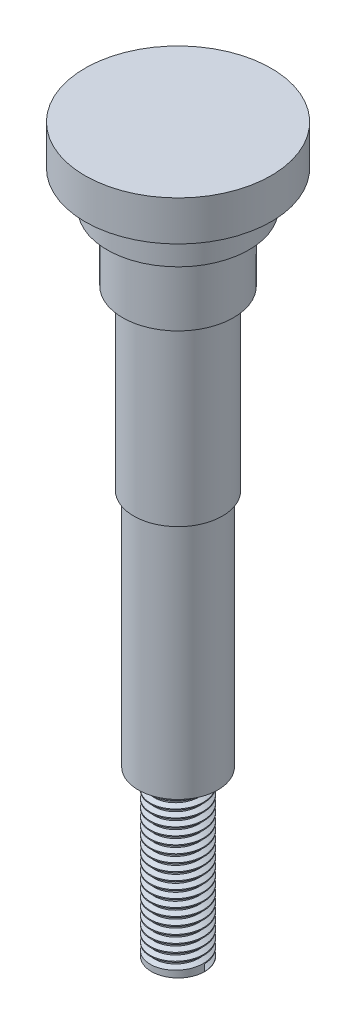
SolidWorks part; units mm, degrees
ref_plane "Front Plane" through (0, 0, 0) normal (0, 0, 1) x (1, 0, 0)
ref_plane "Top Plane" through (0, 0, 0) normal (0, 1, 0) x (1, 0, 0)
ref_plane "Right Plane" through (0, 0, 0) normal (1, 0, 0) x (0, 0, -1)
sketch "Sketch2" plane through (0, 0, 0) normal (0, 1, 0) x (1, 0, 0)
  circle A0 centre (0, 0) radius 21
extrude "Boss-Extrude1" add sketch "Sketch2" along normal blind 9
sketch "Sketch3" plane through (0, 0, 0) normal (0, -1, 0) x (1, 0, 0)
  circle A0 centre (0, 0) radius 16
extrude "Boss-Extrude2" add sketch "Sketch3" along normal blind 8
sketch "Sketch4" plane through (0, -8, 0) normal (0, -1, 0) x (1, 0, 0)
  circle A0 centre (0, 0) radius 12.5
extrude "Boss-Extrude3" add sketch "Sketch4" along normal blind 15
sketch "Sketch5" plane through (0, -23, 0) normal (0, -1, 0) x (1, 0, 0)
  circle A0 centre (0, 0) radius 10
extrude "Boss-Extrude4" add sketch "Sketch5" along normal blind 40
sketch "Sketch6" plane through (0, -63, 0) normal (0, -1, 0) x (1, 0, 0)
  circle A0 centre (0, 0) radius 9
extrude "Boss-Extrude5" add sketch "Sketch6" along normal blind 54
sketch "Sketch7" plane through (0, -117, 0) normal (0, -1, 0) x (1, 0, 0)
  circle A0 centre (0, 0) radius 6
extrude "Boss-Extrude6" add sketch "Sketch7" along normal blind 37
thread "Thread1" pitch 1.75 method cut profile "Thread Profile1" start angle 0, offset 0, length 0, pitch 1.75, diameter 12
ref_plane "Plane1" through (6, -154, 0) normal (0, 0, 1) x (1, 0, 0)
sketch "Thread Profile1" plane through (6, -154, 0) normal (0, 0, 1) x (1, 0, 0)
  line L0 (0, 0) -> (0, 1.75) construction
  line L11 (0, 0) -> (0, 1.5312)
  line L12 (0, 1.5312) -> (-0.9472, 0.9844)
  line L13 (-0.9472, 0.9844) -> (-0.9472, 0.5469)
  line L15 (-0.9472, 0.5469) -> (0, 0)
  line L17 (-0.9472, 0.7656) -> (0, 0.7656) construction
  point P2 (0, 0)
  dimension "Pitch" = 1.75
  dimension "Profile_Angle" = 60
  dimension "Profile_Land" = 0.4375
  dimension "Profile_Height" = 0.9472
